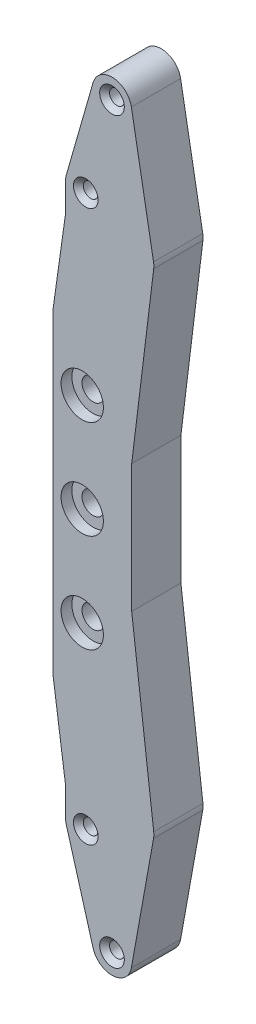
SolidWorks part; units mm, degrees
ref_plane "Front Plane" through (0, 0, 0) normal (0, 0, 1) x (1, 0, 0)
ref_plane "Top Plane" through (0, 0, 0) normal (0, 1, 0) x (1, 0, 0)
ref_plane "Right Plane" through (0, 0, 0) normal (1, 0, 0) x (0, 0, -1)
sketch "Sketch1" plane through (0, 0, 0) normal (0, 0, 1) x (1, 0, 0)
  line L11 (20.4367, 18.7086) -> (19.3445, 24.7763)
  line L12 (19.3445, 24.7763) -> (15.9367, 43.7086)
  line L13 (8.1549, 44.1026) -> (2.7115, 25.1189)
  line L17 (2.5518, 24) -> (2.5271, 18.0017)
  line L18 (2.5271, 18.0017) -> (0, 0)
  line L19 (0, 0) -> (0, -64)
  line L20 (0, -32) -> (16, -32) construction
  line L22 (16, -19) -> (20.4703, 17.5139)
  line L23 (16, -19) -> (16, -45)
  line L24 (16, -45) -> (20.4703, -81.5139)
  line L25 (2.5271, -82.0017) -> (0, -64)
  line L26 (2.5518, -88) -> (2.5271, -82.0017)
  line L27 (8.1549, -108.1026) -> (2.7115, -89.1189)
  line L28 (19.3445, -88.7763) -> (15.9367, -107.7086)
  line L29 (20.4367, -82.7086) -> (19.3445, -88.7763)
  arc A1 (15.9367, 43.7086) -> (8.1549, 44.1026) centre (12, 43) ccw
  arc A2 (2.5518, 24) -> (2.7115, 25.1189) centre (6.673, 23.983) cw
  arc A3 (20.4703, 17.5139) -> (20.4367, 18.7086) centre (16.5, 18) ccw
  arc A4 (20.4703, -81.5139) -> (20.4367, -82.7086) centre (16.5, -82) cw
  arc A5 (2.5518, -88) -> (2.7115, -89.1189) centre (6.673, -87.983) ccw
  arc A6 (15.9367, -107.7086) -> (8.1549, -108.1026) centre (12, -107) cw
  point P39 (6.7206, -1.2896)
  point P46 (0, 0)
  dimension "D4" = 4.1212
  dimension "D6" = 4
  dimension "D14" = 4
  dimension "D1" = 32
  dimension "D2" = 18.0017
  dimension "D3" = 5.9983
  dimension "D5" = 19.7487
  dimension "D7" = 19.2366
  dimension "D8" = 6.1652
  dimension "D9" = 36.7865
  dimension "D10" = 13
  dimension "D11" = 16
  dimension "D12" = 187.991
  dimension "D13" = 173.02
  dimension "D15" = 197.184
extrude "Boss-Extrude1" add sketch "Sketch1" against normal blind 10
hole_wizard "CBORE for M4 SBHCS1" positions "Sketch2" profile "Sketch3" counterbore size "M4" standard "ANSI Metric" end condition through all
sketch "Sketch2" plane through (0, 0, 0) normal (0, 0, 1) x (1, 0, 0)
  line L0 (5.95, -32) -> (0, -32) construction
  line L1 (0, 0) -> (0, -64) construction
  line L3 (5.95, -12) -> (5.95, -32) construction
  line L7 (5.95, -52) -> (5.95, -32) construction
  point P0 (5.95, -32)
  point P2 (5.95, -12)
  point P4 (5.95, -52)
  dimension "D1" = 5.95
  dimension "D2" = 20
sketch "Sketch3" plane through (5.95, -32, 0) normal (1, 0, 0) x (0, -1, 0)
  line L0 (0, 0) -> (0, 10)
  line L1 (0, 10) -> (2.25, 10)
  line L3 (2.25, 10) -> (2.25, 2.2)
  line L4 (2.25, 2.2) -> (4.3, 2.2)
  line L5 (4.3, 2.2) -> (4.3, 0)
  line L7 (4.3, 0) -> (0, 0)
  line L11 (0, -6.35) -> (0, 107.95) construction
  dimension "Thru Hole Dia." = 4.5
  dimension "Thru Hole Depth" = 10
  dimension "C'Bore Dia." = 8.6
  dimension "C'Bore Depth" = 2.2
hole_wizard "CSK for M3 SFHCS1" positions "Sketch4" profile "Sketch5" countersink size "M3" standard "ANSI Metric" end condition through all
sketch "Sketch4" plane through (0, 0, 0) normal (0, 0, 1) x (1, 0, 0)
  point P0 (12, -107)
  point P3 (6.673, -87.983)
  point P6 (6.673, 23.983)
  point P9 (12, 43)
sketch "Sketch5" plane through (12, -107, 0) normal (1, 0, 0) x (0, -1, 0)
  line L0 (0, 0) -> (0, 10)
  line L1 (0, 10) -> (1.5, 10)
  line L2 (1.5, 10) -> (1.5, 1)
  line L3 (1.5, 1) -> (2.5, 0)
  line L5 (2.5, 0) -> (0, 0)
  line L6 (-1.5, 1) -> (-2.5, 0) construction
  line L11 (0, -6.35) -> (0, 107.95) construction
  dimension "Thru Hole Dia." = 3
  dimension "Thru Hole Depth" = 10
  dimension "Near C'Sink Dia." = 5
  dimension "Near C'Sink Angle" = 90
